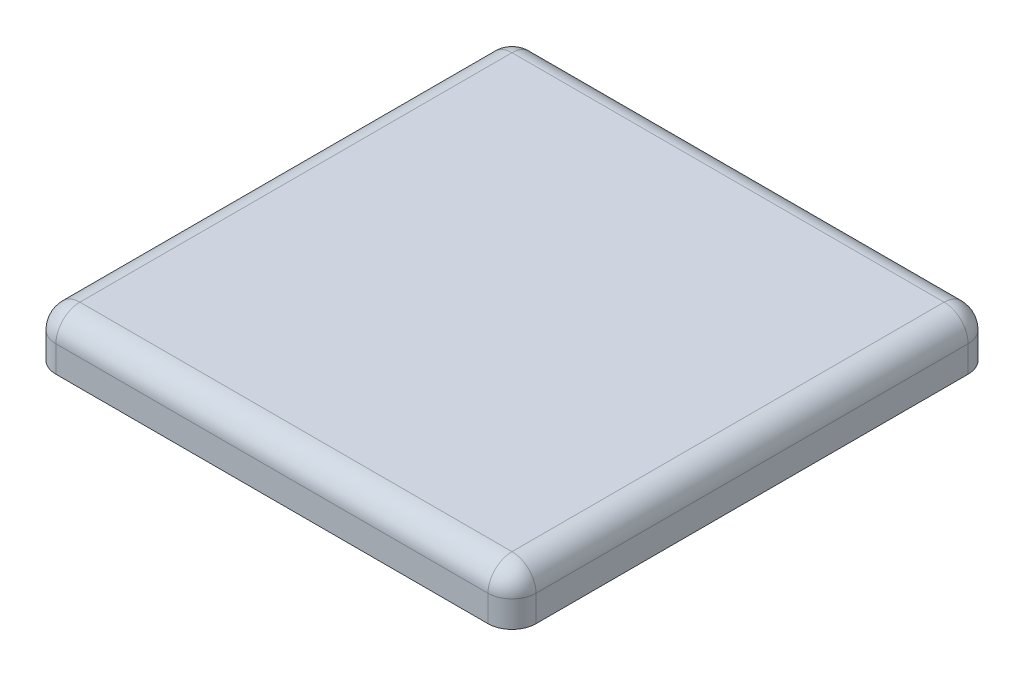
SolidWorks part; units mm, degrees
ref_plane "Ebene vorne" through (0, 0, 0) normal (0, 0, 1) x (1, 0, 0)
ref_plane "Ebene oben" through (0, 0, 0) normal (0, 1, 0) x (1, 0, 0)
ref_plane "Ebene rechts" through (0, 0, 0) normal (1, 0, 0) x (0, 0, -1)
sketch "Skizze1" plane through (0, 0, 0) normal (0, 1, 0) x (1, 0, 0)
  line L0 (0, 48.6612) -> (0, -45.6616) construction
  line L1 (-50.9943, 0) -> (53.6607, 0) construction
  line L2 (-20, -18) -> (-20, 18)
  line L3 (-18, 20) -> (18, 20)
  line L4 (20, -18) -> (20, 18)
  line L5 (-18, -20) -> (18, -20)
  arc A0 (-18, 20) -> (-20, 18) centre (-18, 18) ccw
  arc A1 (18, 20) -> (20, 18) centre (18, 18) cw
  arc A2 (18, -20) -> (20, -18) centre (18, -18) ccw
  arc A3 (-18, -20) -> (-20, -18) centre (-18, -18) cw
  point P8 (-20, 0)
  point P13 (0, 20)
  point P20 (0, -20)
  point P21 (20, 0)
  dimension "D1" = 2
  dimension "D2" = 40
extrude "Aufsatz-Linear austragen1" add sketch "Skizze1" along normal blind 4.2
fillet "Verrundung1" radius 2 8 edges at (19.4142, 4.2, 19.4142) (0, 4.2, 20) (-19.4142, 4.2, 19.4142) (-20, 4.2, 0) (-19.4142, 4.2, -19.4142) (0, 4.2, -20) (19.4142, 4.2, -19.4142) (20, 4.2, 0)
sketch "Skizze2" plane through (0, 0, 0) normal (0, -1, 0) x (1, 0, 0)
  circle A0 centre (0, 0) radius 3.5
  dimension "D1" = 7
extrude "Aufsatz-Linear austragen2" add sketch "Skizze2" along normal blind 10
chamfer "Fase1" distance 3 angle 20 1 edges at (0, -10, -3.5) first distance on face at (0, -10, -3.5)
